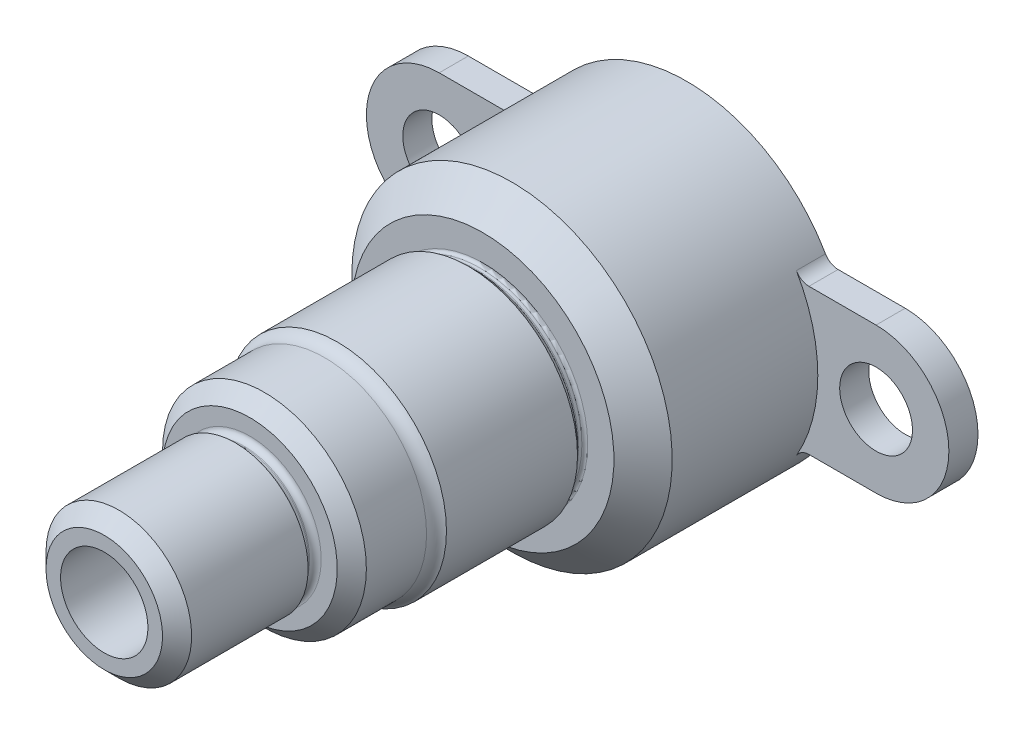
SolidWorks part; units mm, degrees
ref_plane "Спереди" through (0, 0, 0) normal (0, 0, 1) x (1, 0, 0)
ref_plane "Сверху" through (0, 0, 0) normal (0, 1, 0) x (1, 0, 0)
ref_plane "Справа" through (0, 0, 0) normal (1, 0, 0) x (0, 0, -1)
sketch "Эскиз1" plane through (0, 0, 0) normal (1, 0, 0) x (0, 0, -1)
  line L0 (-28.643, 0) -> (42.3762, 0) construction
  line L1 (30, 11) -> (16, 11)
  line L2 (30, 10) -> (25, 10)
  line L3 (30, 11) -> (30, 10)
  line L4 (18, 8) -> (25, 8)
  line L5 (25, 8) -> (25, 10)
  line L6 (-10, 5) -> (0, 5)
  line L7 (-10, 3) -> (2, 3)
  line L10 (-10, 3) -> (-10, 5)
  line L11 (2, 3) -> (2, 6)
  line L12 (2, 6) -> (18, 6)
  line L13 (18, 6) -> (18, 8)
  line L14 (0, 5) -> (0, 7.5)
  line L15 (0, 7.5) -> (16, 7.5)
  line L16 (16, 7.5) -> (16, 11)
  dimension "D1" = 40
  dimension "D2" = 22
  dimension "D3" = 20
  dimension "D4" = 2
  dimension "D5" = 5
  dimension "D6" = 10
  dimension "D7" = 6
  dimension "D8" = 10
  dimension "D9" = 14
  dimension "D10" = 2
  dimension "D11" = 2
  dimension "D12" = 1.5
  dimension "D13" = 15
revolve "Повернуть1" add sketch "Эскиз1" angle 360 about L0
sketch "Эскиз2" plane through (0, 0, 0) normal (0, 1, 0) x (1, 0, 0)
  line L0 (4.5, 0) -> (5, 0)
  line L1 (5, 0) -> (5, -1)
  line L2 (5, -10) -> (5, 0) construction
  line L4 (4.5, -0.7) -> (4.5, 0)
  line L5 (0, 0) -> (0, -7.3244) construction
  line L6 (5, -1) -> (4.5, -0.7)
  dimension "D1" = 0.5
  dimension "D2" = 1
  dimension "D3" = 0.7
revolve "Вырез-Повернуть1" cut sketch "Эскиз2" angle 360 about L5
fillet "Скругление1" radius 0.4 2 edges at (-4.5, 0, 0) (-4.5, 0, 0.7)
sketch "Эскиз3" plane through (0, 0, 0) normal (0, 1, 0) x (1, 0, 0)
  line L0 (0, 0) -> (0, 36.5873) construction
  line L1 (-10, 25) -> (-10.2236, 25)
  line L2 (-10.2236, 25) -> (-10.2236, 25.5)
  line L4 (-10, 25.7) -> (-10, 25)
  line L7 (-10.2236, 25.5) -> (-10, 25.7)
  line L8 (-10, 30) -> (-10, 25) construction
  dimension "D1" = 0.3
  dimension "D2" = 0.5
  dimension "D3" = 0.7
revolve "Вырез-Повернуть2" cut sketch "Эскиз3" angle 360 about L0
fillet "Скругление2" radius 0.2 2 edges at (10.2236, 0, -25.5) (10.2236, 0, -25)
sketch "Эскиз4" plane through (0, 0, -30) normal (0, 0, -1) x (-1, 0, 0)
  line L0 (-22.9294, 0) -> (20.459, 0) construction
  line L1 (-15, 5) -> (-9.798, 5)
  line L2 (-15, -5) -> (-9.798, -5)
  arc A0 (-9.798, 5) -> (-9.798, -5) centre (0, 0) ccw
  circle A1 centre (0, 0) radius 11 construction
  arc A2 (-15, 5) -> (-15, -5) centre (-15, 0) ccw
  dimension "D1" = 15
  dimension "D2" = 5
extrude "Бобышка-Вытянуть1" add sketch "Эскиз4" against normal blind 2
hole_wizard "Диаметр отверстия Ø5.0 (5)1" positions "Эскиз5" profile "Эскиз6" hole size "Ø5.0" standard "Ansi Metric" end condition through all
sketch "Эскиз5" plane through (0, 0, -30) normal (0, 0, -1) x (-1, 0, 0)
  point P0 (-15, 0)
sketch "Эскиз6" plane through (15, 0, -30) normal (1, 0, 0) x (0, 1, 0)
  line L0 (0, 0) -> (0, 40)
  line L1 (0, 40) -> (2.5, 40)
  line L2 (2.5, 40) -> (2.5, 0)
  line L5 (2.5, 0) -> (0, 0)
  line L11 (0, -6.35) -> (0, 107.95) construction
  dimension "Диаметр сквозного отверстия" = 5
  dimension "Глубина сквозного отверстия" = 40
mirror "Зеркальное отражение1" about plane through (0, 0, 0) normal (1, 0, 0) of "Бобышка-Вытянуть1", "Диаметр отверстия Ø5.0 (5)1"
chamfer "Фаска2" distance 0.5 angle 45 1 edges at (10, 0, -30)
fillet "Скругление4" radius 1 4 edges at (-9.798, -5, -29) (-9.798, 5, -29) (9.798, -5, -29) (9.798, 5, -29)
chamfer "Фаска1" distance 1 angle 45 3 edges at (5, 0, 10) (8, 0, -25) (6, 0, -18)
sketch "Эскиз7" plane through (0, 0, 0) normal (1, 0, 0) x (0, 0, -1)
  line L0 (0, 7.5) -> (6, 7.5)
  line L1 (6, 7.5) -> (6, 7)
  line L2 (6, 7) -> (0, 7)
  line L3 (0, 7) -> (0, 7.5)
  line L4 (0, 0) -> (18.304, 0) construction
  dimension "D1" = 6
  dimension "D2" = 14
revolve "Вырез-Повернуть3" cut sketch "Эскиз7" angle 360 about L4
cosmetic thread "Условное изображение резьбы1" parameters "D2"=12.344
fillet "Скругление5" radius 1 1 edges at (7, 0, -6)
chamfer "Фаска3" distance 1 angle 45 1 edges at (7, 0, 0)
sketch "Эскиз8" plane through (0, 0, 0) normal (1, 0, 0) x (0, 0, -1)
  line L0 (0, 0) -> (38.2899, 0) construction
  line L1 (15.8, 7) -> (15.5828, 7)
  line L3 (16, 7.2) -> (16, 7.5)
  line L4 (16, 7.5) -> (15, 7.5)
  line L5 (15, 7.5) -> (15.4414, 7.0586)
  arc A0 (15.4414, 7.0586) -> (15.5828, 7) centre (15.5828, 7.2) ccw
  arc A1 (15.8, 7) -> (16, 7.2) centre (15.8, 7.2) ccw
  dimension "D4" = 0.2
  dimension "D1" = 0.5
  dimension "D2" = 1
  dimension "D3" = 45
revolve "Вырез-Повернуть4" cut sketch "Эскиз8" angle 360 about L0
chamfer "Фаска4" distance 2 angle 45 1 edges at (11, 0, -16)
fillet "Скругление6" radius 1 2 edges at (6, 0, -2) (8, 0, -18)
